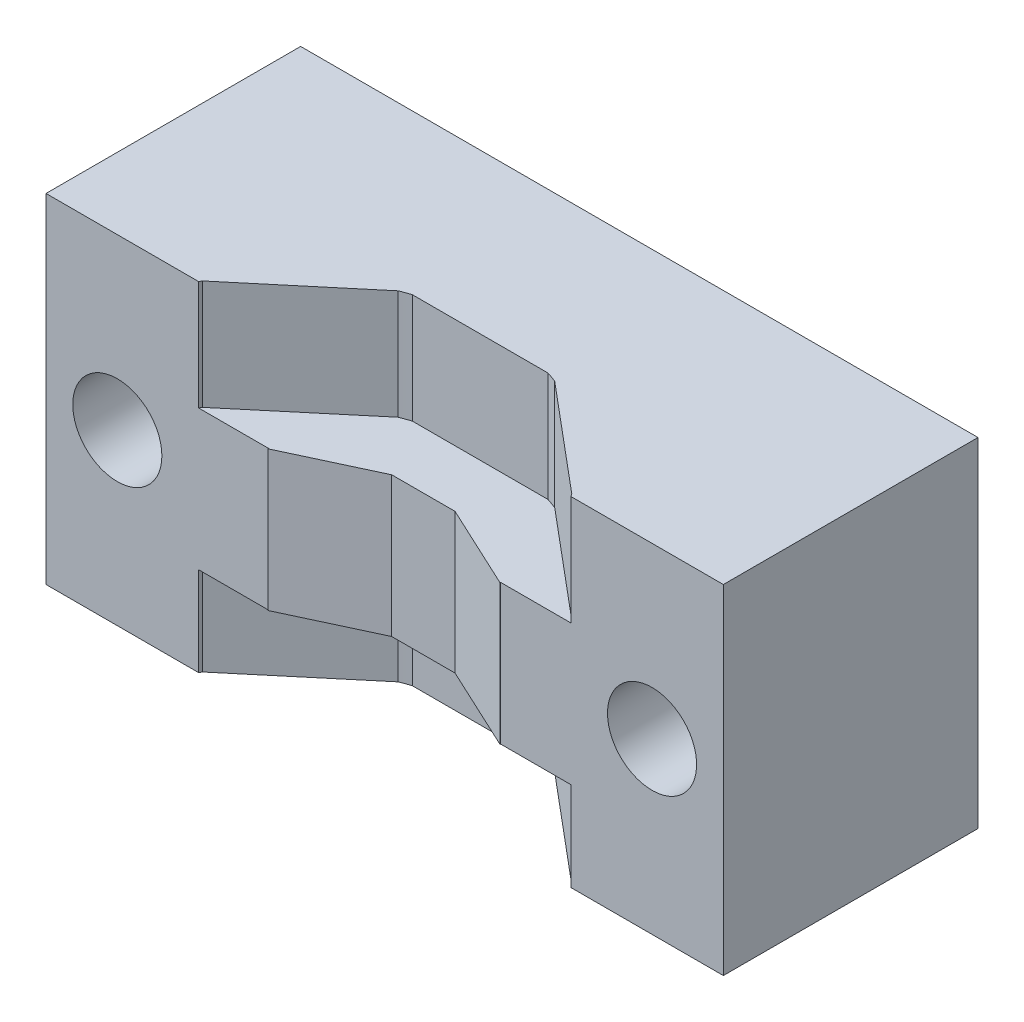
SolidWorks part; units mm, degrees
note: The reader was unsure of these and kept them because the rebuilt part matched: shared geometry of "Esboço3<3>".
ref_plane "Plano frontal" through (0, 0, 0) normal (0, 0, 1) x (1, 0, 0)
ref_plane "Plano superior" through (0, 0, 0) normal (0, 1, 0) x (1, 0, 0)
ref_plane "Plano direito" through (0, 0, 0) normal (1, 0, 0) x (0, 0, -1)
ref_plane "Plano1" through (0, 0, -2) normal (0, 0, -1) x (-1, 0, 0)
sketch "Esboço1" plane through (0, 0, -2) normal (0, 0, -1) x (-1, 0, 0)
  line L1 (13.3, -6.65) -> (-13.3, -6.65)
  line L2 (13.3, -6.65) -> (13.3, 6.65)
  line L3 (13.3, 6.65) -> (-13.3, 6.65)
  line L4 (-13.3, -6.65) -> (-13.3, 6.65)
  line L5 (13.3, -6.65) -> (-13.3, 6.65) construction
  line L6 (13.3, 6.65) -> (-13.3, -6.65) construction
  point P0 (0, 0)
  dimension "D1" = 13.3
  dimension "D2" = 26.6
extrude "Ressalto-extrusão1" add sketch "Esboço1" against normal blind 10
sketch "Esboço2" plane through (0, 0, -2) normal (0, 0, -1) x (-1, 0, 0)
  line L0 (0, 0) -> (0, 6.65) construction
  line L1 (13.3, 6.65) -> (-13.3, 6.65) construction
  line L2 (0, 0) -> (-10.5, 0) construction
  circle A0 centre (-10.5, 0) radius 1.75
  circle A1 centre (10.5, 0) radius 1.75
  dimension "D1" = 3.5
  dimension "D2" = 10.5
extrude "Corte-extrusão1" cut sketch "Esboço2" against normal through all
sketch "Esboço3" plane through (0, 6.65, 0) normal (0, 1, 0) x (1, 0, 0)
  line L0 (0, -8) -> (0, -12.3) construction
  line L1 (-13.3, -8) -> (13.3, -8) construction
  circle A0 centre (0, -12.3) radius 8.48
  circle A1 centre (0, -12.3) radius 6.25
  dimension "D2" = 16.96
  dimension "D3" = 12.5
  dimension "D1" = 4.3
extrude "Corte-extrusão2" cut sketch "Esboço3" against normal blind 4.3
extrude "Corte-extrusão3" cut sketch "Esboço3<3>" against normal blind 9.8
sketch "Esboço3<3>" plane through (0, 6.65, 0) normal (0, 1, 0) x (1, 0, 0) same geometry as "Esboço3"
sketch "Esboço4" plane through (0, -6.65, 0) normal (0, -1, 0) x (1, 0, 0)
  circle A0 centre (0, 12.3) radius 8.48 construction
  circle A1 centre (0, 12.3) radius 8.48
extrude "Corte-extrusão4" cut sketch "Esboço4" against normal up to surface (3.5 mm away) up to face at (0, -3.15, 7.025)
sketch "Esboço5" plane through (0, 6.65, 0) normal (0, 1, 0) x (1, 0, 0)
  line L0 (-7.2496, -7.9007) -> (-3.0736, -4.3966)
  line L1 (-5.1616, -6.1487) -> (-5.4508, -5.8039) construction
  line L2 (0, 0) -> (0, -6.05) construction
  line L3 (7.2496, -7.9007) -> (3.0736, -4.3966)
  line L4 (-2.6661, -4.25) -> (2.6661, -4.25)
  line L5 (0, -4.25) -> (0, -3.82) construction
  line L6 (-7.2496, -7.9007) -> (-6.9609, -4.3966)
  line L7 (-6.9609, -4.3966) -> (-3.0736, -4.3966)
  line L8 (-2.6661, -4.25) -> (0, -3.025)
  line L9 (0, -3.025) -> (2.6661, -4.25)
  line L10 (7.2496, -7.9007) -> (6.9609, -4.3966)
  line L11 (6.9609, -4.3966) -> (3.0736, -4.3966)
  arc A0 (7.3089, -8) -> (-7.3089, -8) centre (0, -12.3) ccw construction
  arc A1 (7.3089, -8) -> (-7.3089, -8) centre (0, -12.3) ccw construction
  arc A2 (4.5357, -8) -> (-4.5357, -8) centre (0, -12.3) ccw construction
  dimension "D1" = 0.45
  dimension "D2" = 40
  dimension "D3" = 0.43
extrude "Ressalto-extrusão2" add sketch "Esboço5" against normal through all
sketch "Esboço6" plane through (0, 2.35, 0) normal (0, 1, 0) x (1, 0, 0)
  line L0 (0, 0) -> (0, -6.05) construction
  line L1 (-4.5614, -8.0272) -> (-1.2433, -6.48)
  line L2 (-2.9023, -7.2536) -> (-3.0841, -6.8639) construction
  line L3 (-4.5614, -8.0272) -> (-3.5824, -5.9716)
  line L4 (-3.5824, -5.9716) -> (-0.3949, -6.0625)
  line L5 (4.5614, -8.0272) -> (3.5824, -5.9716)
  line L6 (3.5824, -5.9716) -> (0.3949, -6.0625)
  line L7 (4.5614, -8.0272) -> (1.2433, -6.48)
  line L8 (-1.2433, -6.48) -> (1.2433, -6.48)
  line L9 (0, -6.05) -> (0, -6.48) construction
  line L10 (-0.3949, -6.0625) -> (0.3949, -6.0625)
  arc A0 (4.5357, -8) -> (-4.5357, -8) centre (0, -12.3) ccw construction
  dimension "D1" = 0.43
  dimension "D2" = 25
  dimension "D3" = 0.43
extrude "Ressalto-extrusão3" add sketch "Esboço6" against normal up to surface (5.5 mm away) up to face at (0, -3.15, 6.3139)
sketch "Esboço7" plane through (0, 2.35, 0) normal (0, 1, 0) x (1, 0, 0)
  line L0 (0.3949, -6.0625) -> (-0.3949, -6.0625) construction
  line L1 (-0.6736, -6.2763) -> (0.6736, -6.2763)
  line L2 (-0.6736, -6.2763) -> (-0.6736, -5.8487)
  line L3 (-0.6736, -5.8487) -> (0.6736, -5.8487)
  line L4 (0.6736, -6.2763) -> (0.6736, -5.8487)
  line L5 (-0.6736, -6.2763) -> (0.6736, -5.8487) construction
  line L6 (-0.6736, -5.8487) -> (0.6736, -6.2763) construction
  point P0 (0, -6.0625)
extrude "Ressalto-extrusão4" add sketch "Esboço7" against normal up to surface (5.5 mm away) up to face at (0, -3.15, 6.7217)
